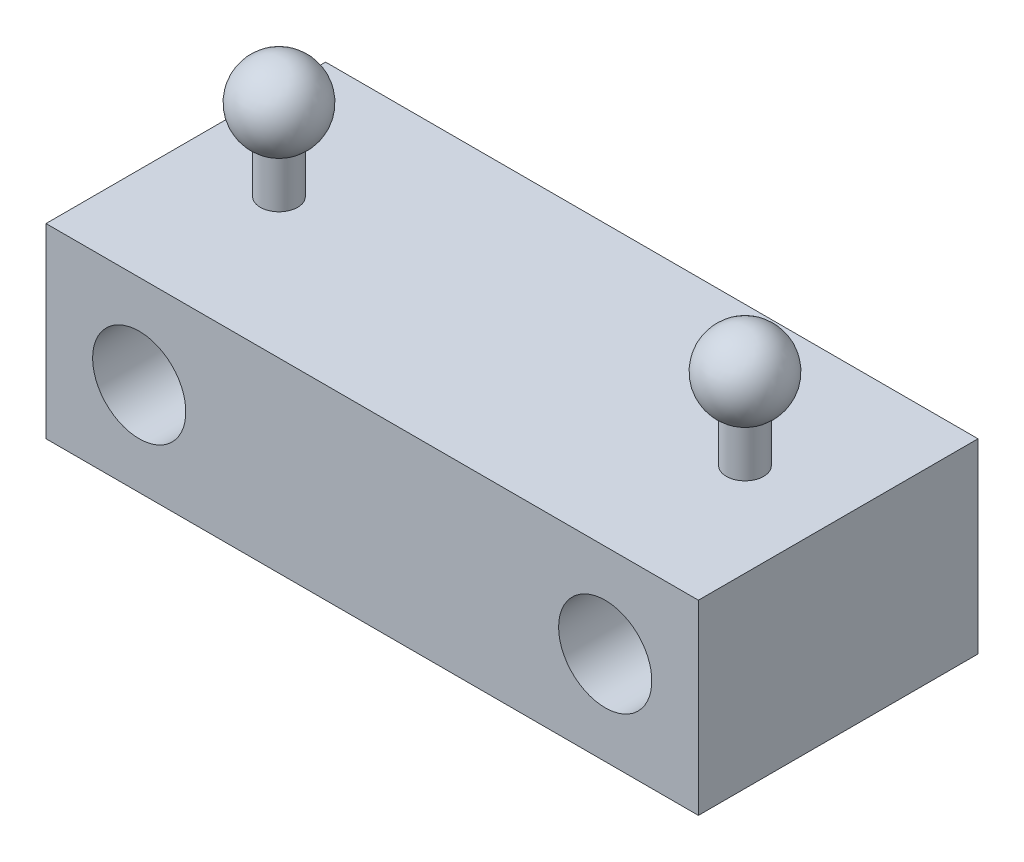
SolidWorks part; units mm, degrees
ref_plane "Front Plane" through (0, 0, 0) normal (0, 0, 1) x (1, 0, 0)
ref_plane "Top Plane" through (0, 0, 0) normal (0, 1, 0) x (1, 0, 0)
ref_plane "Right Plane" through (0, 0, 0) normal (1, 0, 0) x (0, 0, -1)
sketch "Sketch1" plane through (0, 0, 0) normal (0, 1, 0) x (1, 0, 0)
  line L1 (-35, 15) -> (35, 15)
  line L2 (-35, 15) -> (-35, -15)
  line L3 (-35, -15) -> (35, -15)
  line L4 (35, 15) -> (35, -15)
  line L5 (-35, 15) -> (35, -15) construction
  line L6 (-35, -15) -> (35, 15) construction
  point P0 (0, 0)
  dimension "D1" = 30
  dimension "D2" = 70
extrude "Boss-Extrude1" add sketch "Sketch1" along normal blind 20 contours L1 L4 L3 L2
sketch "Sketch2" plane through (0, 0, -15) normal (0, 0, -1) x (-1, 0, 0)
  line L2 (-35, 20) -> (-35, 0) construction
  line L3 (35, 0) -> (-35, 0) construction
  circle A0 centre (-25, 10) radius 5
  circle A1 centre (25, 10) radius 5
  dimension "D1" = 10
  dimension "D2" = 50
  dimension "D3" = 10
  dimension "D4" = 10
extrude "Cut-Extrude1" cut sketch "Sketch2" against normal up to next
sketch "Sketch3" plane through (0, 20, 0) normal (0, 1, 0) x (1, 0, 0)
  circle A0 centre (-25, 0) radius 2
  circle A1 centre (25, 0) radius 2
  dimension "D1" = 50
  dimension "D2" = 25
extrude "Boss-Extrude2" add sketch "Sketch3" along normal blind 5
dome "Dome1" faces to dome 1 distance 8 reverse direction no elliptical dome no face at (-25, 25, 2) parameters "D1"=8
dome "Dome2" faces to dome 1 distance 8 reverse direction no elliptical dome no face at (25, 25, 2) parameters "D1"=8
